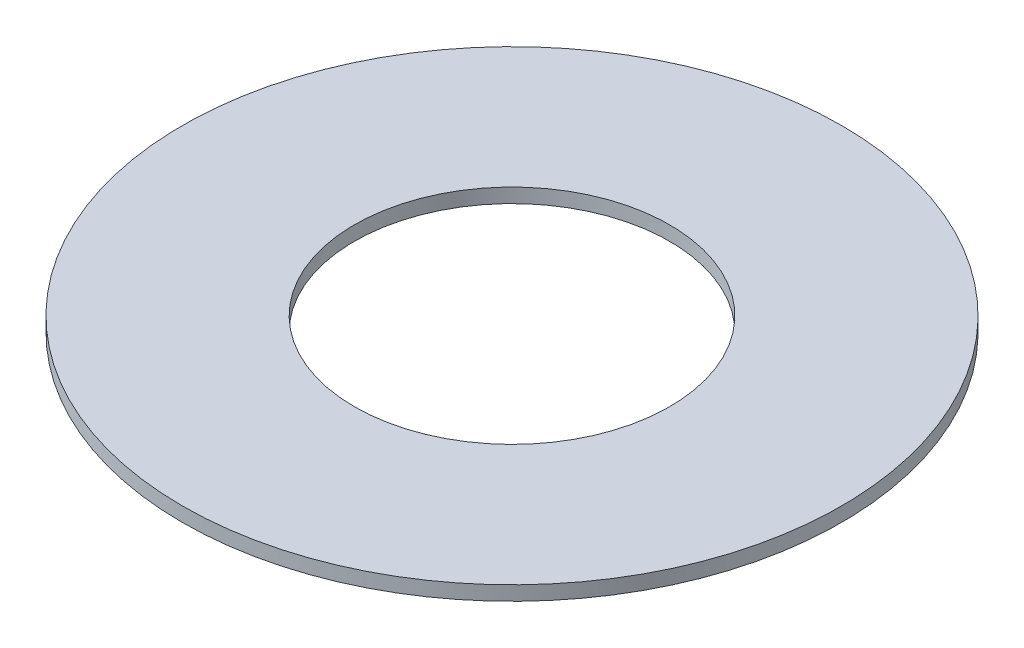
SolidWorks part; units mm, degrees
material "PTFE (general)"
ref_plane "Front Plane" through (0, 0, 0) normal (0, 0, 1) x (1, 0, 0)
ref_plane "Top Plane" through (0, 0, 0) normal (0, 1, 0) x (1, 0, 0)
ref_plane "Right Plane" through (0, 0, 0) normal (1, 0, 0) x (0, 0, -1)
sketch "Sketch1" plane through (0, 0, 0) normal (0, 1, 0) x (1, 0, 0)
  circle A0 centre (0, 0) radius 46
  circle A1 centre (0, 0) radius 22
  dimension "D1" = 44
  dimension "D2" = 92
extrude "Boss-Extrude1" add sketch "Sketch1" along normal blind 2
